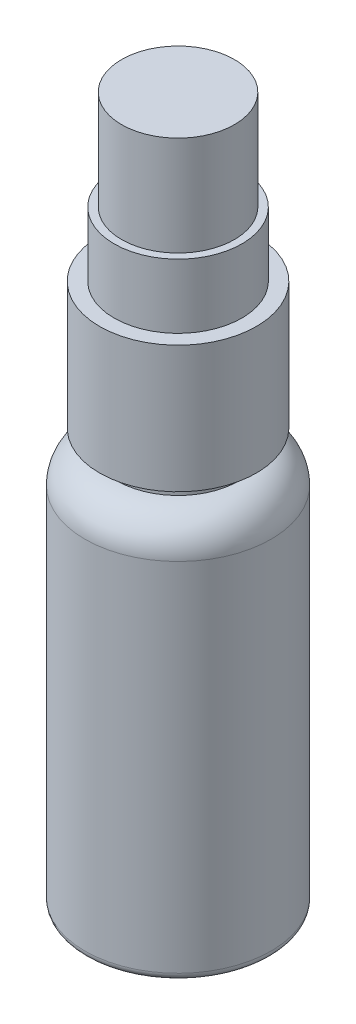
SolidWorks part; units mm, degrees
other "Markup1"
sketch "Sketch2" plane through (-11.875, 89.975, 11.875) normal (-0.9195, 0.3318, 0.2107) x (0.2261, 0.0082, 0.9741)
ref_plane "Front Plane" through (0, 0, 0) normal (0, 0, 1) x (1, 0, 0)
ref_plane "Top Plane" through (0, 0, 0) normal (0, 1, 0) x (1, 0, 0)
ref_plane "Right Plane" through (0, 0, 0) normal (1, 0, 0) x (0, 0, -1)
ref_axis "Axis1" through (0, -4.4988, 0) along (0, 1, 0)
sketch "Sketch1" plane through (0, 0, 0) normal (0, 0, 1) x (1, 0, 0)
  line L0 (9.75, 0) -> (10.875, 0)
  line L1 (11.875, 1) -> (11.875, 46.5)
  line L3 (0, -4.4988) -> (0, 94.4737) construction
  line L4 (8.75, 1) -> (8.75, 1.4096)
  line L5 (7.75, 2.4096) -> (0, 2.4096)
  line L6 (0, 65.8) -> (0, 2.4096)
  line L11 (0, 89.975) -> (0, 65.8)
  line L12 (7.5, 50.875) -> (7.75, 50.875)
  line L13 (7.75, 50.875) -> (7.75, 52.875)
  line L14 (7.75, 52.875) -> (10, 52.875)
  line L15 (10, 52.875) -> (10, 69.075)
  line L16 (10, 69.075) -> (8.15, 69.075)
  line L17 (8.15, 69.075) -> (8.15, 77.275)
  line L18 (8.15, 77.275) -> (7.2, 77.275)
  line L19 (7.2, 77.275) -> (7.2, 89.975)
  line L20 (0, 89.975) -> (7.2, 89.975)
  arc A0 (11.875, 46.5) -> (7.5, 50.875) centre (7.5, 46.5) ccw
  arc A1 (8.75, 1.4096) -> (7.75, 2.4096) centre (7.75, 1.4096) ccw
  arc A2 (9.75, 0) -> (8.75, 1) centre (9.75, 1) cw
  arc A3 (10.875, 0) -> (11.875, 1) centre (10.875, 1) ccw
  dimension "D1" = 1
  dimension "D2" = 1
  dimension "D3" = 7.75
  dimension "D4" = 8.15
  dimension "D5" = 11.875
  dimension "D6" = 2
  dimension "D7" = 16.2
  dimension "D8" = 10
  dimension "D9" = 8.2
  dimension "D10" = 12.7
  dimension "D11" = 7.2
  dimension "D12" = 45.5
revolve "Revolve1" add sketch "Sketch1" angle 360 about L6
